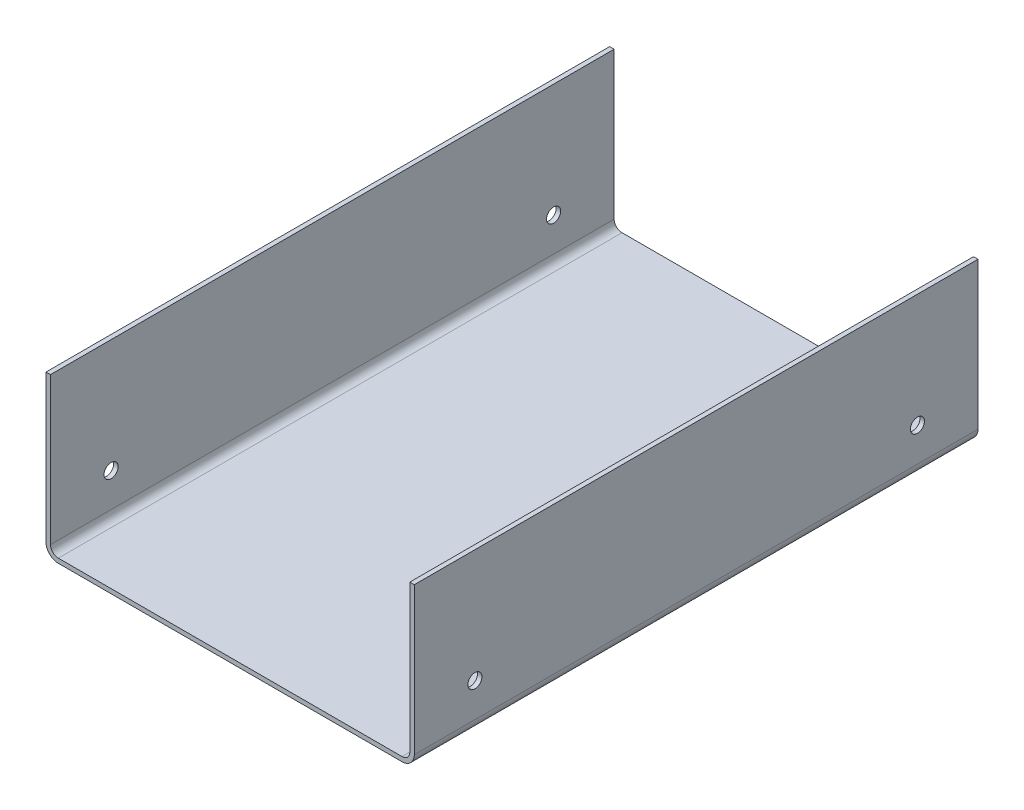
SolidWorks part; units mm, degrees
material "5052-H32"
ref_plane "Front Plane" through (0, 0, 0) normal (0, 0, 1) x (1, 0, 0)
ref_plane "Top Plane" through (0, 0, 0) normal (0, 1, 0) x (1, 0, 0)
ref_plane "Right Plane" through (0, 0, 0) normal (1, 0, 0) x (0, 0, -1)
sketch "Sketch1" plane through (0, 0, 0) normal (0, 0, 1) x (1, 0, 0)
  line L8 (127.5, 110) -> (127.5, 0)
  line L9 (-127.5, 0) -> (127.5, 0)
  line L10 (-127.5, 0) -> (-127.5, 110)
  line L11 (130.68, 110) -> (130.68, -3.18)
  line L12 (-130.68, -3.18) -> (130.68, -3.18)
  line L13 (-130.68, -3.18) -> (-130.68, 110)
  line L14 (127.5, 110) -> (130.68, 110)
  line L15 (-127.5, 110) -> (-130.68, 110)
  point P5 (0, 0)
  dimension "D2" = 110
  dimension "D4" = 110
  dimension "D3" = 255
  dimension "D1" = 3.18
extrude "Boss-Extrude1" add sketch "Sketch1" along normal blind 400
fillet "Fillet2" radius 5.5563 2 edges at (127.5, 0, 200) (-127.5, 0, 200)
fillet "Fillet3" radius 8.73 2 edges at (-130.68, -3.18, 200) (130.68, -3.18, 200)
sketch "Sketch2" plane through (130.68, 0, 0) normal (1, 0, 0) x (0, 0, -1)
  line L1 (-400, 5.55) -> (-400, 110) construction
  line L2 (0, 5.55) -> (0, 110) construction
  line L4 (-357, 29.5) -> (-357, 0) construction
  line L7 (-43, 29.5) -> (-43, 0) construction
  circle A0 centre (-357, 29.5) radius 5
  circle A1 centre (-43, 29.5) radius 5
  dimension "D3" = 10
  dimension "D4" = 10
  dimension "D1" = 43
  dimension "D2" = 29.5
  dimension "D5" = 43
  dimension "D6" = 29.5
extrude "Cut-Extrude1" cut sketch "Sketch2" against normal up to surface (261.36 mm away) up to face at (-130.68, 57.775, 200)
equation "\"W\"= 255"
equation "\"L\"= 400"
equation "\"Offset\"= 30"
equation "\"H\"= 110"
equation "\"Compartment Width\"= 80"
equation "\"T\"= 4.7625 * 2 / 3"
equation "\"Inside Fillet Radius\"= 5.55625"
equation "\"Hole\"=15"
equation "\"Wheel to Wall\"= 50"
equation "\"D3@Sketch1\"=\"W\""
equation "\"D2@Sketch1\"=\"H\""
equation "\"D4@Sketch1\"=\"H\""
equation "\"D1@Boss-Extrude1\"=\"L\""
equation "\"D1@Fillet2\"=\"Inside Fillet Radius\""
equation "\"D1@Fillet3\"=\"Inside Fillet Radius\"+\"T\""
